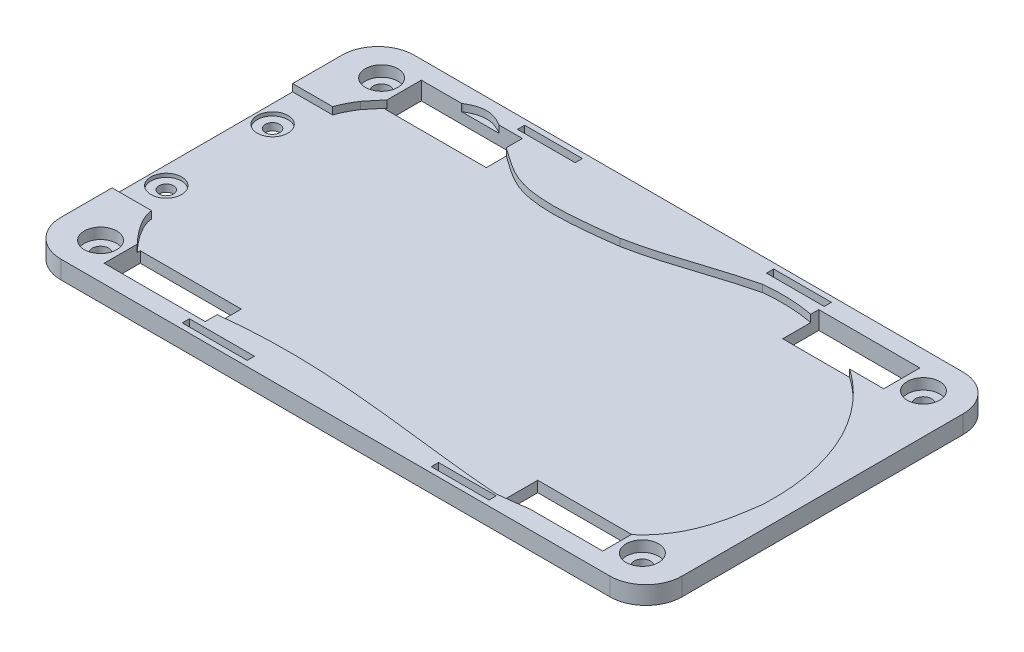
SolidWorks part; units mm, degrees
ref_plane "Front Plane" through (0, 0, 0) normal (0, 0, 1) x (1, 0, 0)
ref_plane "Top Plane" through (0, 0, 0) normal (0, 1, 0) x (1, 0, 0)
ref_plane "Right Plane" through (0, 0, 0) normal (1, 0, 0) x (0, 0, -1)
sketch "Sketch1" plane through (0, 0, 0) normal (0, 1, 0) x (1, 0, 0)
  line L1 (-78.1571, 35.933) -> (-78.1571, -14.1122)
  line L2 (78.9797, 0.0343) -> (-78.1571, 0.0343) construction
  line L3 (-77.1571, 35.7646) -> (-77.1571, -14.1122)
  line L4 (78.9797, -0.9657) -> (-78.1571, -0.9657)
  arc A1 (37.8695, -35.2975) -> (39.5975, -35.2134) centre (38.2635, -25.6055) ccw
  arc A2 (37.9263, -34.299) -> (39.4753, -34.2207) centre (38.2635, -25.6055) ccw
  spline S0 degree 1 poles (-77.1571, -14.1122) (-56.919, -31.9168) knots 0 0 1 1 construction
  spline S1 degree 1 poles (-56.919, -31.9168) (37.9263, -34.299) knots 0 0 1 1 construction
  spline S2 degree 1 poles (39.4753, -34.2207) (77.9849, 0.1477) knots 0 0 1 1 construction
  spline S3 degree 1 poles (77.9849, 0.1477) (25.0602, 52.8732) knots 0 0 1 1 construction
  spline S4 degree 1 poles (25.0602, 52.8732) (-5.6593, 44.1904) knots 0 0 1 1 construction
  spline S5 degree 1 poles (-5.6593, 44.1904) (-43.9853, 50.6886) knots 0 0 1 1 construction
  spline S6 degree 1 poles (-43.9853, 50.6886) (-59.7702, 54.7238) knots 0 0 1 1 construction
  spline S7 degree 1 poles (-59.7702, 54.7238) (-74.5158, 41.0521) knots 0 0 1 1 construction
  spline S8 degree 1 poles (-74.5158, 41.0521) (-77.1571, 35.7646) knots 0 0 1 1 construction
  spline S9 degree 3 poles (-77.1571, -14.1122) (-77.1565, -14.3701) (-77.1092, -14.8732) (-76.8359, -15.9559) (-76.1879, -17.5008) (-75.044, -19.4183) (-73.152, -22.0092) (-70.3495, -25.0822) (-66.8736, -28.0972) (-63.6864, -30.2141) (-61.0019, -31.4062) (-58.8274, -31.848) (-57.5718, -31.8794) (-56.919, -31.9168) knots 0.000484 0.000484 0.000484 0.000484 0.031521 0.062558 0.124632 0.186706 0.248781 0.372929 0.497077 0.621225 0.745373 0.869521 0.993669 0.993669 0.993669 0.993669
  spline S10 degree 3 poles (-56.919, -31.9168) (-56.6769, -31.8873) (-56.2021, -31.8274) (-55.1791, -31.687) (-53.8294, -31.4877) (-52.0759, -31.2184) (-49.5744, -30.8354) (-46.1465, -30.3372) (-41.5825, -29.7813) (-36.5976, -29.3261) (-29.4274, -28.913) (-19.5571, -28.8468) (-6.4839, -29.5875) (5.2448, -30.7865) (15.023, -31.9295) (22.521, -32.809) (30.1538, -33.642) (35.3408, -34.1075) (37.9263, -34.299) knots 0.000538 0.000538 0.000538 0.000538 0.016152 0.031766 0.062993 0.094221 0.125449 0.187904 0.250359 0.312815 0.37527 0.50018 0.625091 0.750001 0.812457 0.874912 0.937367 0.999822 0.999822 0.999822 0.999822
  spline S11 degree 3 poles (39.4753, -34.2207) (41.0079, -34.0574) (44.09, -33.7147) (50.0835, -32.8429) (57.0969, -31.1859) (64.2184, -27.8839) (69.7763, -23.1857) (73.0497, -18.2789) (74.9177, -14.0269) (75.9805, -10.7732) (76.7509, -7.5724) (77.1995, -5.064) (77.4798, -3.2279) (77.6607, -1.9649) (77.8261, -0.8108) (77.9301, -0.1834) (77.9849, 0.1477) knots -0.000309 -0.000309 -0.000309 -0.000309 0.063093 0.126495 0.253299 0.380104 0.506908 0.633712 0.697114 0.760516 0.823918 0.88732 0.919021 0.950722 0.982423 1.014124 1.014124 1.014124 1.014124
  spline S12 degree 3 poles (77.9849, 0.1477) (78.0286, 1.2633) (78.0637, 3.5224) (77.9426, 6.757) (77.6596, 9.9047) (77.0733, 13.9671) (75.9626, 18.7836) (73.4433, 25.9357) (69.0206, 33.8098) (62.0495, 41.4932) (53.7895, 47.3444) (44.6121, 51.2947) (34.9036, 53.2804) (28.3113, 53.2357) (25.0602, 52.8732) knots 0.000169 0.000169 0.000169 0.000169 0.031414 0.062658 0.093902 0.125147 0.187635 0.250124 0.375101 0.500079 0.625056 0.750034 0.875011 0.999988 0.999988 0.999988 0.999988
  spline S13 degree 3 poles (25.0602, 52.8732) (19.8954, 51.6294) (12.3224, 49.1317) (2.1607, 45.9713) (-3.0371, 44.6913) (-5.6593, 44.1904) knots 0.000659 0.000659 0.000659 0.000659 0.498067 0.746772 0.995476 0.995476 0.995476 0.995476
  spline S14 degree 3 poles (-5.6593, 44.1904) (-6.6879, 44.0461) (-8.7287, 43.7719) (-12.9633, 43.2668) (-18.1826, 42.7952) (-23.9015, 42.6322) (-28.8306, 42.9899) (-32.9666, 43.9514) (-35.9177, 45.2914) (-38.1959, 46.6779) (-39.9392, 47.8658) (-41.507, 48.9798) (-42.8638, 49.9292) (-43.6163, 50.4405) (-43.9853, 50.6886) knots -0.000196 -0.000196 -0.000196 -0.000196 0.062587 0.12537 0.250936 0.376501 0.502067 0.627632 0.753198 0.815981 0.878764 0.941546 0.972938 1.004329 1.004329 1.004329 1.004329
  spline S15 degree 3 poles (-43.9853, 50.6886) (-44.2445, 50.8673) (-44.7682, 51.2325) (-45.7507, 51.9331) (-46.8912, 52.7591) (-48.146, 53.6496) (-49.6971, 54.6811) (-51.4608, 55.6487) (-53.4077, 56.2593) (-55.2517, 56.3574) (-56.711, 56.0808) (-57.7948, 55.7138) (-58.5465, 55.3915) (-59.2299, 55.0428) (-59.5837, 54.8359) (-59.7702, 54.7238) knots -0.002497 -0.002497 -0.002497 -0.002497 0.029066 0.060629 0.123754 0.18688 0.250006 0.376257 0.502509 0.62876 0.755012 0.818137 0.881263 0.944389 1.007515 1.007515 1.007515 1.007515
  spline S16 degree 3 poles (-78.1571, -14.1122) (-78.1559, -14.7524) (-77.9173, -15.9777) (-77.0678, -17.9828) (-75.8538, -20.0098) (-73.8827, -22.6985) (-70.9901, -25.8584) (-67.4096, -28.9504) (-64.0991, -31.1349) (-61.2379, -32.3904) (-59.243, -32.7789) (-57.8421, -32.8756) (-57.2118, -32.9007) (-56.8882, -32.9203) knots 0.000409 0.000409 0.000409 0.000409 0.062843 0.125276 0.18771 0.250143 0.375011 0.499878 0.624745 0.749612 0.874479 0.936913 0.999346 0.999346 0.999346 0.999346
  spline S17 degree 3 poles (-56.8882, -32.9203) (-56.6427, -32.8908) (-56.1603, -32.8306) (-55.1309, -32.6904) (-53.7754, -32.491) (-52.0233, -32.2221) (-49.5292, -31.8398) (-46.1189, -31.3427) (-41.5829, -30.7872) (-36.6286, -30.3313) (-29.4997, -29.9158) (-19.6749, -29.8441) (-6.6369, -30.5782) (5.0856, -31.7749) (14.8757, -32.919) (22.3927, -33.8009) (30.0532, -34.6371) (35.2704, -35.1052) (37.8695, -35.2975) knots -0.001373 -0.001373 -0.001373 -0.001373 0.014273 0.029919 0.06121 0.092502 0.123794 0.186377 0.24896 0.311543 0.374127 0.499293 0.62446 0.749626 0.81221 0.874793 0.937376 0.99996 0.99996 0.99996 0.99996
  spline S18 degree 3 poles (39.5975, -35.2134) (41.1398, -35.049) (44.2356, -34.7045) (50.3018, -33.8209) (57.4502, -32.1301) (64.7991, -28.7164) (70.5782, -23.8111) (73.9656, -18.7006) (75.8832, -14.3057) (76.9672, -10.962) (77.7479, -7.6914) (78.1997, -5.145) (78.4804, -3.2966) (78.6613, -2.0308) (78.824, -0.9009) (78.9276, -0.2806) (78.9816, 0.0458) knots -0.000086 -0.000086 -0.000086 -0.000086 0.063428 0.126941 0.253967 0.380993 0.50802 0.635046 0.698559 0.762072 0.825585 0.889098 0.920855 0.952612 0.984368 1.016125 1.016125 1.016125 1.016125
  spline S19 degree 3 poles (78.9816, 0.0458) (79.0271, 1.1797) (79.0647, 3.4739) (78.9444, 6.7697) (78.6587, 9.9749) (78.0642, 14.1169) (76.9341, 19.0326) (74.3646, 26.3398) (69.8439, 34.3944) (62.712, 42.2543) (54.2626, 48.2351) (44.8799, 52.2671) (34.9529, 54.2886) (28.2109, 54.2351) (24.8869, 53.8601) knots -0.000407 -0.000407 -0.000407 -0.000407 0.03088 0.062166 0.093453 0.12474 0.187314 0.249888 0.375035 0.500183 0.62533 0.750478 0.875625 1.000773 1.000773 1.000773 1.000773
  spline S20 degree 3 poles (24.8869, 53.8601) (22.2839, 53.2349) (17.1223, 51.77) (6.9788, 48.4835) (-0.6206, 46.1711) (-5.8226, 45.1772) knots -0.001281 -0.001281 -0.001281 -0.001281 0.247714 0.49671 0.9947 0.9947 0.9947 0.9947
  spline S21 degree 3 poles (-5.8226, 45.1772) (-6.8463, 45.0337) (-8.8779, 44.761) (-13.0882, 44.2593) (-18.2643, 43.7927) (-23.9018, 43.6338) (-28.7026, 43.9859) (-32.6523, 44.9085) (-35.4477, 46.177) (-37.6484, 47.5152) (-39.3619, 48.6824) (-40.9248, 49.793) (-42.292, 50.7496) (-43.0505, 51.2651) (-43.4225, 51.5151) knots 0.000305 0.000305 0.000305 0.000305 0.063048 0.125791 0.251276 0.376761 0.502247 0.627732 0.753218 0.815961 0.878703 0.941446 0.972817 1.004189 1.004189 1.004189 1.004189
  spline S22 degree 3 poles (-43.4225, 51.5151) (-43.6786, 51.6918) (-44.1958, 52.0526) (-45.1684, 52.7462) (-46.308, 53.5714) (-47.577, 54.4721) (-49.1727, 55.5335) (-51.0441, 56.5648) (-53.2147, 57.2519) (-55.3195, 57.3652) (-56.9568, 57.0533) (-58.1477, 56.6506) (-58.9689, 56.2985) (-59.5708, 55.992) (-60.0059, 55.7483) (-60.1862, 55.6406) (-60.2803, 55.5839) knots -0.002294 -0.002294 -0.002294 -0.002294 0.029245 0.060783 0.12386 0.186936 0.250013 0.376167 0.50232 0.628473 0.754627 0.817704 0.88078 0.943857 0.975396 1.006934 1.006934 1.006934 1.006934
  spline S23 degree 3 poles (-60.2803, 55.5839) (-60.715, 55.3297) (-61.582, 54.801) (-63.2222, 53.7187) (-65.9105, 51.7373) (-69.2431, 48.741) (-72.0244, 45.6929) (-73.7392, 43.6279) (-74.6657, 42.4756) (-75.1049, 41.9202) (-75.3265, 41.639) knots 0.000427 0.000427 0.000427 0.000427 0.063268 0.126109 0.251792 0.503158 0.754524 0.880206 0.943048 1.005889 1.005889 1.005889 1.005889
  spline S24 degree 3 poles (-59.7702, 54.7238) (-60.1936, 54.4761) (-61.0386, 53.9612) (-62.6368, 52.9072) (-65.2587, 50.9763) (-68.5171, 48.0498) (-71.2443, 45.0657) (-73.1899, 42.7247) (-74.0698, 41.6179) (-74.5158, 41.0521) knots 0.000174 0.000174 0.000174 0.000174 0.062881 0.125589 0.251004 0.501833 0.752662 0.878077 1.003492 1.003492 1.003492 1.003492
  spline S25 degree 3 poles (-74.5158, 41.0521) (-75.0658, 40.2217) (-76.0765, 38.4779) (-76.8336, 36.6875) (-77.1571, 35.7646) knots 0.499549 0.499549 0.499549 0.499549 0.499766 0.499983 0.499983 0.499983 0.499983
  spline S26 degree 3 poles (-75.3265, 41.639) (-75.92, 40.746) (-77.0064, 38.8701) (-77.815, 36.9314) (-78.1571, 35.933) knots 0.499546 0.499546 0.499546 0.499546 0.49977 0.499995 0.499995 0.499995 0.499995
  point P0 (0.4631, 0.0343)
  dimension "D1" = 1
sketch "Sketch6" plane through (0, 0, 0) normal (0, 1, 0) x (1, 0, 0)
  line L0 (-78.1571, 35.933) -> (-78.1571, -14.1122) construction
  line L1 (73.9816, 59.5839) -> (-78.1571, 59.5839)
  line L2 (83.9816, 49.5839) -> (83.9816, -28.2975)
  line L3 (73.9816, -38.2975) -> (-78.1571, -38.2975)
  line L4 (-88.1571, 49.5839) -> (-88.1571, -28.2975)
  arc A0 (-78.1571, -38.2975) -> (-88.1571, -28.2975) centre (-78.1571, -28.2975) cw
  arc A1 (-88.1571, 49.5839) -> (-78.1571, 59.5839) centre (-78.1571, 49.5839) cw
  arc A2 (73.9816, 59.5839) -> (83.9816, 49.5839) centre (73.9816, 49.5839) cw
  arc A3 (83.9816, -28.2975) -> (73.9816, -38.2975) centre (73.9816, -28.2975) cw
  dimension "D5" = 10
  dimension "D1" = 5
  dimension "D2" = 10
  dimension "D3" = 3
  dimension "D4" = 4
extrude "Boss-Extrude2" add sketch "Sketch6" along normal blind 6.5
extrude "Cut-Extrude1" cut sketch "Sketch1" along normal blind 2.5 contours A2 S11 L4 L3 S9 S10 | S24 S25 L3 L4 S11 S12 S13 S14 S15 region at (0.1139, 0, 15.5782) region at (-2.2602, 0, -23.2786)
sketch "Sketch7" plane through (0, 0, 0) normal (0, -1, 0) x (1, 0, 0)
  line L1 (-76.2189, 14.1122) -> (-91.3452, 14.1122)
  line L2 (-76.2189, 14.1122) -> (-76.2189, -35.933)
  line L3 (-76.2189, -35.933) -> (-91.3452, -35.933)
  line L4 (-91.3452, 14.1122) -> (-91.3452, -35.933)
extrude "Cut-Extrude2" cut sketch "Sketch7" against normal up to surface (2.5 mm away) contours L2 L1 L4 L3 up to face at (-19.4492, 2.5, -12.7234)
sketch "Sketch8" plane through (0, 6.5, 0) normal (0, 1, 0) x (1, 0, 0)
  line L0 (83.9816, 10.6432) -> (-88.1571, 10.6432) construction
  line L1 (83.9816, -28.2975) -> (83.9816, 49.5839) construction
  line L2 (-88.1571, 49.5839) -> (-88.1571, -28.2975) construction
  line L3 (-2.0877, 59.5839) -> (-2.0877, -38.2975) construction
  line L4 (73.9816, 59.5839) -> (-78.1571, 59.5839) construction
  line L5 (-78.1571, -38.2975) -> (73.9816, -38.2975) construction
  line L7 (78.9816, 54.5839) -> (38.9816, 54.5839)
  line L8 (78.9816, 54.5839) -> (78.9816, 44.5839)
  line L9 (78.9816, 44.5839) -> (38.9816, 44.5839)
  line L10 (38.9816, 54.5839) -> (38.9816, 44.5839)
  line L22 (38.9816, 49.5839) -> (78.9816, 49.5839) construction
  line L23 (66.9816, 54.5839) -> (66.9816, 44.5839)
  circle A1 centre (72.9816, 49.5839) radius 3.5
  dimension "D6" = 7
  dimension "D1" = 10
  dimension "D2" = 40
  dimension "D3" = 5
  dimension "D4" = 5
  dimension "D5" = 6
  dimension "D7" = 6
sketch "Sketch9" plane through (0, 0, 0) normal (0, -1, 0) x (1, 0, 0)
  circle A0 centre (72.9816, -49.5839) radius 4.5
  dimension "D1" = 9
extrude "Cut-Extrude5" cut sketch "Sketch9" against normal blind 3.5
sketch "Sketch10" plane through (0, 3.5, 0) normal (0, -1, 0) x (1, 0, 0)
  circle A0 centre (72.9816, -49.5839) radius 2.25
  dimension "D1" = 4.5
extrude "Cut-Extrude6" cut sketch "Sketch10" against normal blind 21
extrude "Cut-Extrude8" cut sketch "Sketch8" against normal blind 42 contours L23 L7 L10 L9 region at (52.9816, 6.5, -49.5839)
extrude "Cut-Extrude9" cut sketch "Sketch8<3>" against normal blind 1 contours L7 L23 L9 L8 A1 region at (78.8254, 6.5, -49.5839)
sketch "Sketch8<3>" plane through (0, 6.5, 0) normal (0, 1, 0) x (1, 0, 0) same geometry as "Sketch8"
sketch "Sketch12" plane through (0, 6.5, 0) normal (0, 1, 0) x (1, 0, 0)
  line L0 (-88.1571, 10.6432) -> (83.9816, 10.6432) construction
  line L1 (-88.1571, 49.5839) -> (-88.1571, -28.2975) construction
  line L2 (83.9816, -28.2975) -> (83.9816, 49.5839) construction
  line L3 (-2.0877, 59.5839) -> (-2.0877, -36.8461) construction
  line L4 (73.9816, 59.5839) -> (-78.1571, 59.5839) construction
ref_plane "Plane1" through (0, 0, -10.6432) normal (0, 0, 1) x (1, 0, 0)
ref_plane "Plane2" through (-2.0877, 0, 0) normal (-1, 0, 0) x (0, 0, 1)
mirror "Mirror1" about plane through (0, 0, -10.6432) normal (0, 0, 1) of "Cut-Extrude5", "Cut-Extrude6", "Cut-Extrude8", "Cut-Extrude9"
mirror "Mirror2" about plane through (-2.0877, 0, 0) normal (-1, 0, 0) of "Mirror1", "Cut-Extrude9", "Cut-Extrude8", "Cut-Extrude6", "Cut-Extrude5"
sketch "Sketch13" plane through (0, 6.5, 0) normal (0, 1, 0) x (1, 0, 0)
  line L0 (-83.1571, 44.5839) -> (-43.1571, 44.5839) construction
  line L1 (58.9816, 39.5839) -> (-63.1571, 39.5839)
  line L2 (58.9816, 39.5839) -> (58.9816, -18.2975)
  line L3 (58.9816, -18.2975) -> (-63.1571, -18.2975)
  line L4 (-63.1571, 39.5839) -> (-63.1571, -18.2975)
  line L5 (58.9816, 39.5839) -> (-63.1571, -18.2975) construction
  line L6 (58.9816, -18.2975) -> (-63.1571, 39.5839) construction
  line L7 (-83.1571, -23.2975) -> (-43.1571, -23.2975) construction
  line L8 (83.9816, -28.2975) -> (83.9816, 49.5839) construction
  line L9 (-88.1571, 49.5839) -> (-88.1571, -28.2975) construction
  point P0 (-2.0877, 10.6432)
  dimension "D1" = 5
  dimension "D2" = 5
  dimension "D3" = 25
  dimension "D4" = 25
extrude "Cut-Extrude10" cut sketch "Sketch13" against normal blind 1
sketch "Sketch14" plane through (0, 5.5, 0) normal (0, 1, 0) x (1, 0, 0)
  line L0 (-63.1571, 10.6432) -> (58.9816, 10.6432) construction
  line L1 (-63.1571, 39.5839) -> (-63.1571, -18.2975) construction
  line L2 (58.9816, -18.2975) -> (58.9816, 39.5839) construction
  line L3 (-63.1571, -9.3568) -> (58.9816, -9.3568) construction
  line L4 (-63.1571, 10.6432) -> (58.9816, 10.6432) construction
  line L5 (-63.1571, 30.6432) -> (58.9816, 30.6432) construction
  circle A1 centre (-12.0877, 10.6432) radius 2.5
  circle A2 centre (-32.0877, 10.6432) radius 2.5
  circle A3 centre (-52.0877, 10.6432) radius 2.5
  circle A4 centre (-12.0877, 10.6432) radius 2.5
  circle A5 centre (-32.0877, 10.6432) radius 2.5
  circle A6 centre (7.9123, 10.6432) radius 2.5
  circle A7 centre (-12.0877, 10.6432) radius 2.5
  circle A8 centre (27.9123, 10.6432) radius 2.5
  circle A9 centre (7.9123, 10.6432) radius 2.5
  circle A10 centre (7.9123, 10.6432) radius 2.5
  circle A11 centre (27.9123, 10.6432) radius 2.5
  circle A12 centre (47.9123, 10.6432) radius 2.5
  circle A13 centre (-12.0877, -9.3568) radius 2.5
  circle A14 centre (-32.0877, -9.3568) radius 2.5
  circle A15 centre (-52.0877, -9.3568) radius 2.5
  circle A16 centre (-12.0877, -9.3568) radius 2.5
  circle A17 centre (-32.0877, -9.3568) radius 2.5
  circle A18 centre (7.9123, -9.3568) radius 2.5
  circle A19 centre (-12.0877, -9.3568) radius 2.5
  circle A20 centre (27.9123, -9.3568) radius 2.5
  circle A21 centre (7.9123, -9.3568) radius 2.5
  circle A22 centre (7.9123, -9.3568) radius 2.5
  circle A23 centre (27.9123, -9.3568) radius 2.5
  circle A24 centre (47.9123, -9.3568) radius 2.5
  circle A25 centre (-12.0877, 10.6432) radius 2.5
  circle A26 centre (-32.0877, 10.6432) radius 2.5
  circle A27 centre (-52.0877, 10.6432) radius 2.5
  circle A28 centre (-12.0877, 10.6432) radius 2.5
  circle A29 centre (-32.0877, 10.6432) radius 2.5
  circle A30 centre (7.9123, 10.6432) radius 2.5
  circle A31 centre (-12.0877, 10.6432) radius 2.5
  circle A32 centre (27.9123, 10.6432) radius 2.5
  circle A33 centre (7.9123, 10.6432) radius 2.5
  circle A34 centre (7.9123, 10.6432) radius 2.5
  circle A35 centre (27.9123, 10.6432) radius 2.5
  circle A36 centre (47.9123, 10.6432) radius 2.5
  circle A37 centre (-12.0877, 30.6432) radius 2.5
  circle A38 centre (-32.0877, 30.6432) radius 2.5
  circle A39 centre (-52.0877, 30.6432) radius 2.5
  circle A40 centre (-12.0877, 30.6432) radius 2.5
  circle A41 centre (-32.0877, 30.6432) radius 2.5
  circle A42 centre (7.9123, 30.6432) radius 2.5
  circle A43 centre (-12.0877, 30.6432) radius 2.5
  circle A44 centre (27.9123, 30.6432) radius 2.5
  circle A45 centre (7.9123, 30.6432) radius 2.5
  circle A46 centre (7.9123, 30.6432) radius 2.5
  circle A47 centre (27.9123, 30.6432) radius 2.5
  circle A48 centre (47.9123, 30.6432) radius 2.5
  point P8 (-2.0877, 10.6432)
  point P37 (-2.0877, -9.3568)
  point P64 (-2.0877, 10.6432)
  point P91 (-2.0877, 30.6432)
  dimension "D2" = 5
  dimension "D1" = 10
  dimension "D3" = 3
  dimension "D4" = 4
  dimension "D5" = 2
  dimension "D6" = 2
extrude "Cut-Extrude11" cut sketch "Sketch14" against normal blind 57 contours A39 | A42 | A44 | A48 | A12 | A6 | A1 | A2 | A3 | A24 | A20 | A18 | A13 | A14 | A15 | A38 | A37 | A8 region at (-12.0877, 5.5, -10.6432) region at (-32.0877, 5.5, -10.6432) region at (-52.0877, 5.5, -10.6432) region at (7.9123, 5.5, -10.6432) region at (47.9123, 5.5, -10.6432) region at (-12.0877, 5.5, 9.3568) region at (-32.0877, 5.5, 9.3568) region at (-52.0877, 5.5, 9.3568) region at (7.9123, 5.5, 9.3568) region at (27.9123, 5.5, 9.3568) region at (47.9123, 5.5, 9.3568) region at (-52.0877, 5.5, -30.6432) region at (7.9123, 5.5, -30.6432) region at (27.9123, 5.5, -30.6432) region at (47.9123, 5.5, -30.6432)
sketch "Sketch16" plane through (0, 0, 0) normal (0, -1, 0) x (1, 0, 0)
  line L0 (78.9816, -0.5458) -> (78.9816, -79.1994) construction
  line L1 (22.9816, -56.0839) -> (-37.6427, -56.0839) construction
  line L2 (73.9816, -59.5839) -> (-78.1571, -59.5839) construction
  line L3 (38.9816, -54.3238) -> (38.9816, 38.2975) construction
  line L4 (38.9816, -59.5839) -> (38.9816, -54.3238) construction
  line L5 (38.9816, -56.0839) -> (22.9816, -56.0839)
  line L6 (38.9816, -56.0839) -> (38.9816, -58.0839)
  line L7 (38.9816, -58.0839) -> (22.9816, -58.0839)
  line L8 (22.9816, -56.0839) -> (22.9816, -58.0839)
  line L9 (-78.1571, 38.2975) -> (73.9816, 38.2975) construction
  line L10 (22.9816, -56.0839) -> (22.9816, 38.2975) construction
  line L12 (38.9816, 36.7975) -> (22.9816, 36.7975)
  line L13 (38.9816, 36.7975) -> (38.9816, 34.7975)
  line L14 (38.9816, 34.7975) -> (22.9816, 34.7975)
  line L15 (22.9816, 36.7975) -> (22.9816, 34.7975)
  line L16 (22.9816, 34.7975) -> (-46.0184, 34.7975) construction
  line L17 (-30.0184, -56.0839) -> (-46.0184, -56.0839)
  line L18 (-30.0184, -56.0839) -> (-30.0184, -58.0839)
  line L19 (-30.0184, -58.0839) -> (-46.0184, -58.0839)
  line L20 (-46.0184, -56.0839) -> (-46.0184, -58.0839)
  line L22 (-28.0184, 34.7975) -> (-46.0184, 34.7975)
  line L23 (-28.0184, 34.7975) -> (-28.0184, 36.7975)
  line L24 (-28.0184, 36.7975) -> (-46.0184, 36.7975)
  line L25 (-46.0184, 34.7975) -> (-46.0184, 36.7975)
  dimension "D1" = 40
  dimension "D2" = 16
  dimension "D3" = 1.5
  dimension "D4" = 2
  dimension "D5" = 2
  dimension "D6" = 1.5
  dimension "D7" = 125
  dimension "D8" = 16
  dimension "D9" = 2
  dimension "D10" = 18
  dimension "D11" = 2
extrude "Cut-Extrude12" cut sketch "Sketch16" against normal blind 57
sketch "Sketch17" plane through (0, 5.5, 0) normal (0, 1, 0) x (1, 0, 0)
  line L1 (-99.5963, 69.0247) -> (98.4238, 69.0247)
  line L2 (-99.5963, 69.0247) -> (-99.5963, -53.2143)
  line L3 (-99.5963, -53.2143) -> (98.4238, -53.2143)
  line L4 (98.4238, 69.0247) -> (98.4238, -53.2143)
extrude "Cut-Extrude14" cut sketch "Sketch17" along normal blind 48.5
sketch "Sketch23" plane through (0, 2.5, 0) normal (0, -1, 0) x (1, 0, 0)
  line L0 (-88.1571, -10.9104) -> (-64.7808, -10.9104) construction
  line L1 (-88.1571, -35.933) -> (-88.1571, 14.1122) construction
  circle A0 centre (-83.1571, 4.0896) radius 2
  circle A1 centre (-83.1571, 4.0896) radius 4.25
  dimension "D1" = 4
  dimension "D4" = 8.5
  dimension "D2" = 15
  dimension "D3" = 5
extrude "Cut-Extrude15" cut sketch "Sketch23" against normal blind 48.5 contours A0
extrude "Cut-Extrude16" cut sketch "Sketch23<3>" against normal blind 1
sketch "Sketch23<3>" plane through (0, 2.5, 0) normal (0, -1, 0) x (1, 0, 0) same geometry as "Sketch23"
mirror "Mirror4" about plane through (0, 0, -10.6432) normal (0, 0, 1) of "Cut-Extrude16", "Cut-Extrude15"
sketch "Sketch24" plane through (0, 5.5, 0) normal (0, 1, 0) x (1, 0, 0)
  circle A0 centre (-77.1571, 49.5839) radius 3.25
  circle A1 centre (-77.1571, 49.5839) radius 2.25
  circle A2 centre (72.9816, 49.5839) radius 2.25
  circle A3 centre (72.9816, 49.5839) radius 3.25
  circle A4 centre (72.9816, -28.2975) radius 2.25
  circle A5 centre (-77.1571, -28.2975) radius 2.25
  circle A6 centre (-77.1571, -28.2975) radius 3.25
  circle A7 centre (72.9816, -28.2975) radius 3.25
  dimension "D1" = 6.5
  dimension "D2" = 6.5
  dimension "D3" = 6.5
  dimension "D4" = 6.5
extrude "Boss-Extrude3" add sketch "Sketch24" along normal blind 1
ref_plane "Plane3" through (0, 0, 0) normal (0, -1, 0) x (-1, 0, 0)
mirror "Mirror5" about plane through (0, 0, 0) normal (0, -1, 0) of "Boss-Extrude3", "Mirror4", "Cut-Extrude16", "Cut-Extrude15", "Cut-Extrude14", "Cut-Extrude12", "Cut-Extrude10", "Mirror2", "Mirror1", "Cut-Extrude9", "Cut-Extrude8", "Cut-Extrude6", "Cut-Extrude5", "Cut-Extrude2", "Cut-Extrude1", "Boss-Extrude2", "Cut-Extrude11"
sketch "Sketch25" plane through (0, 5.5, 0) normal (0, 1, 0) x (1, 0, 0)
  line L1 (-109.2871, 73.7066) -> (111.0455, 73.7066)
  line L2 (-109.2871, 73.7066) -> (-109.2871, -75.7235)
  line L3 (-109.2871, -75.7235) -> (111.0455, -75.7235)
  line L4 (111.0455, 73.7066) -> (111.0455, -75.7235)
extrude "Cut-Extrude18" cut sketch "Sketch25" against normal up to surface (5.5 mm away) and the other way blind 10 contours L2 L1 L4 L3 up to plane "Plane3"
ref_plane "Plane4" through (-77.0974, 0, 0) normal (-1, 0, 0) x (0, 0, 1)
ref_plane "Plane6" through (0, 0, -35.933) normal (0, 0, 1) x (1, 0, 0)
sketch "Sketch26" plane through (0, 0, 0) normal (0, 1, 0) x (1, 0, 0)
  line L1 (-104.6518, 69.0589) -> (106.0904, 69.0589)
  line L2 (-104.6518, 69.0589) -> (-104.6518, -52.1551)
  line L3 (-104.6518, -52.1551) -> (106.0904, -52.1551)
  line L4 (106.0904, 69.0589) -> (106.0904, -52.1551)
extrude "Cut-Extrude19" cut sketch "Sketch26" against normal blind 0.5
sketch "Sketch27" plane through (0, -2.5, 0) normal (0, 1, 0) x (1, 0, 0)
  line L1 (-59.9586, 37.3138) -> (59.6605, 37.3138)
  line L2 (-59.9586, 37.3138) -> (-59.9586, -15.8502)
  line L3 (-59.9586, -15.8502) -> (59.6605, -15.8502)
  line L4 (59.6605, 37.3138) -> (59.6605, -15.8502)
extrude "Boss-Extrude4" add sketch "Sketch27" against normal up to surface (3 mm away) up to face at (72.9816, -5.5, 25.0475)
